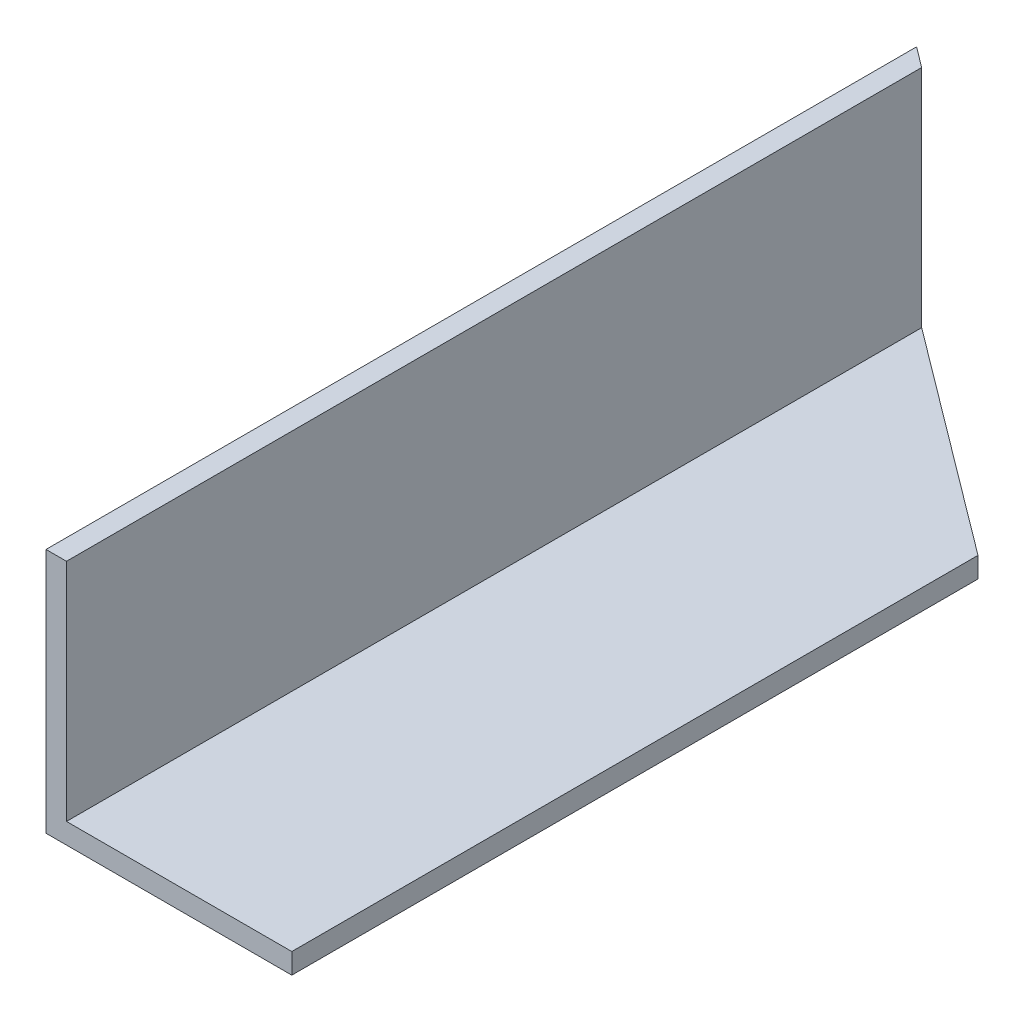
SolidWorks part; units mm, degrees
ref_plane "Front Plane" through (0, 0, 0) normal (0, 0, 1) x (1, 0, 0)
ref_plane "Top Plane" through (0, 0, 0) normal (0, 1, 0) x (1, 0, 0)
ref_plane "Right Plane" through (0, 0, 0) normal (1, 0, 0) x (0, 0, -1)
sketch "Sketch1" plane through (0, 0, 0) normal (0, 0, 1) x (1, 0, 0)
  line L1 (0, 0) -> (38.1, 0)
  line L2 (0, 0) -> (0, 38.1)
  line L3 (0, 38.1) -> (38.1, 38.1)
  line L4 (38.1, 0) -> (38.1, 38.1)
extrude "Boss-Extrude1" add sketch "Sketch1" along normal blind 134.9377
sketch "Sketch2" plane through (0, 0, 134.9377) normal (0, 0, 1) x (1, 0, 0)
  line L1 (38.1, 38.1) -> (3.175, 38.1)
  line L2 (38.1, 38.1) -> (38.1, 3.175)
  line L3 (38.1, 3.175) -> (3.175, 3.175)
  line L4 (3.175, 38.1) -> (3.175, 3.175)
extrude "Cut-Extrude1" cut sketch "Sketch2" against normal blind 134.9377
sketch "Sketch3" plane through (0, 0, 0) normal (0, -1, 0) x (-1, 0, 0)
  line L0 (0, 0) -> (-38.1, 0)
  line L1 (-38.1, 0) -> (-38.1, -28.5751)
  line L2 (-38.1, -134.9377) -> (-38.1, 0) construction
  line L3 (-38.1, -28.5751) -> (0, 0)
  dimension "D1" = 36.87
extrude "Cut-Extrude2" cut sketch "Sketch3" against normal blind 38.1
